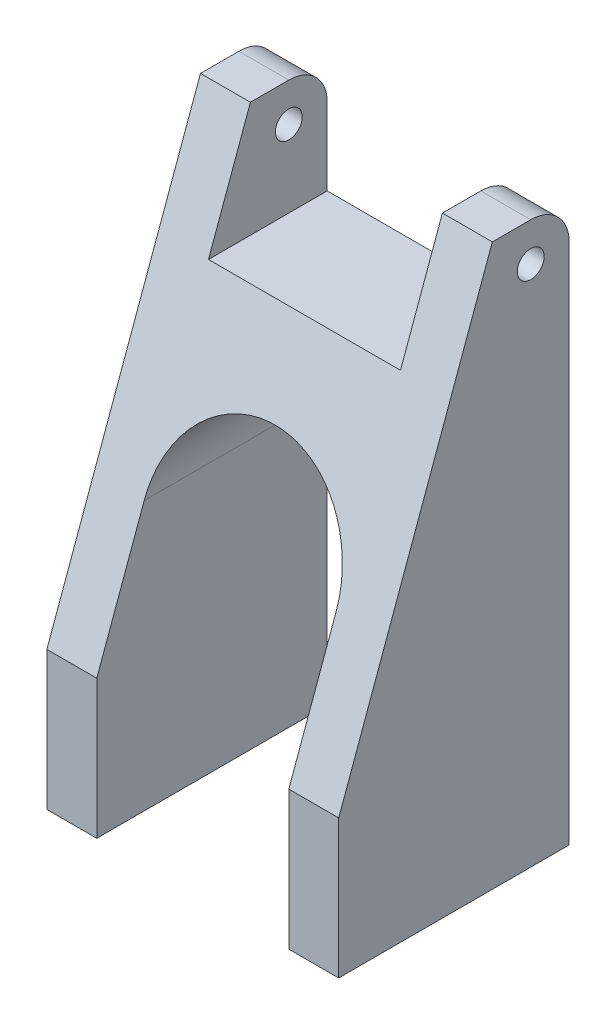
SolidWorks part; units mm, degrees
ref_plane "Front Plane" through (0, 0, 0) normal (0, 0, 1) x (1, 0, 0)
ref_plane "Top Plane" through (0, 0, 0) normal (0, 1, 0) x (1, 0, 0)
ref_plane "Right Plane" through (0, 0, 0) normal (1, 0, 0) x (0, 0, -1)
sketch "Sketch1" plane through (0, 0, 0) normal (0, 0, 1) x (1, 0, 0)
  line L0 (-12.5, 0) -> (-12.5, -35)
  line L1 (-12.5, -35) -> (12.5, -35) construction
  line L2 (12.5, -35) -> (12.5, 0)
  line L4 (-19, -35) -> (-12.5, -35)
  line L5 (12.5, -35) -> (19, -35)
  line L11 (-19, -35) -> (-19, 38)
  line L12 (-19, 38) -> (19, 38)
  line L13 (19, 38) -> (19, -35)
  arc A0 (12.5, 0) -> (-12.5, 0) centre (0, 0) ccw
  point P1 (-19, 49.827)
  dimension "D1" = 25
  dimension "D2" = 38
  dimension "D3" = 73
  dimension "D4" = 35
extrude "Boss-Extrude1" add sketch "Sketch1" along normal blind 30
sketch "Sketch2" plane through (0, -35, 0) normal (0, -1, 0) x (1, 0, 0)
  line L0 (-15, 5) -> (15, 5) construction
  line L1 (0, 0) -> (0, 5) construction
  circle A0 centre (-15, 5) radius 2
  circle A1 centre (15, 5) radius 2
  circle A4 centre (-15, 15) radius 2
  circle A5 centre (15, 15) radius 2
  circle A6 centre (-15, 25) radius 2
  circle A7 centre (15, 25) radius 2
  dimension "D1" = 4
  dimension "D2" = 30
  dimension "D3" = 5
  dimension "D4" = 3
extrude "Cut-Extrude1" cut sketch "Sketch2" against normal blind 15
fillet "Fillet1" radius 5 1 edges at (0, 38, 0)
chamfer "Chamfer1" distance 20 angle 70 1 edges at (0, 38, 30) first distance on face at (0, 38, 17.5)
sketch "Sketch3" plane through (0, 38, 0) normal (0, 1, 0) x (1, 0, 0)
  line L1 (-12.5, 19.7985) -> (12.5, 19.7985)
  line L2 (-12.5, 19.7985) -> (-12.5, -19.7985)
  line L3 (-12.5, -19.7985) -> (12.5, -19.7985)
  line L4 (12.5, 19.7985) -> (12.5, -19.7985)
  line L5 (-12.5, 19.7985) -> (12.5, -19.7985) construction
  line L6 (-12.5, -19.7985) -> (12.5, 19.7985) construction
  point P0 (0, 0)
  dimension "D1" = 25
extrude "Cut-Extrude2" cut sketch "Sketch3" against normal blind 15
sketch "Sketch4" plane through (-19, 0, 0) normal (-1, 0, 0) x (0, 0, 1)
  circle A1 centre (5, 33) radius 1.75
  dimension "D1" = 3.5
extrude "Cut-Extrude3" cut sketch "Sketch4" against normal through all
